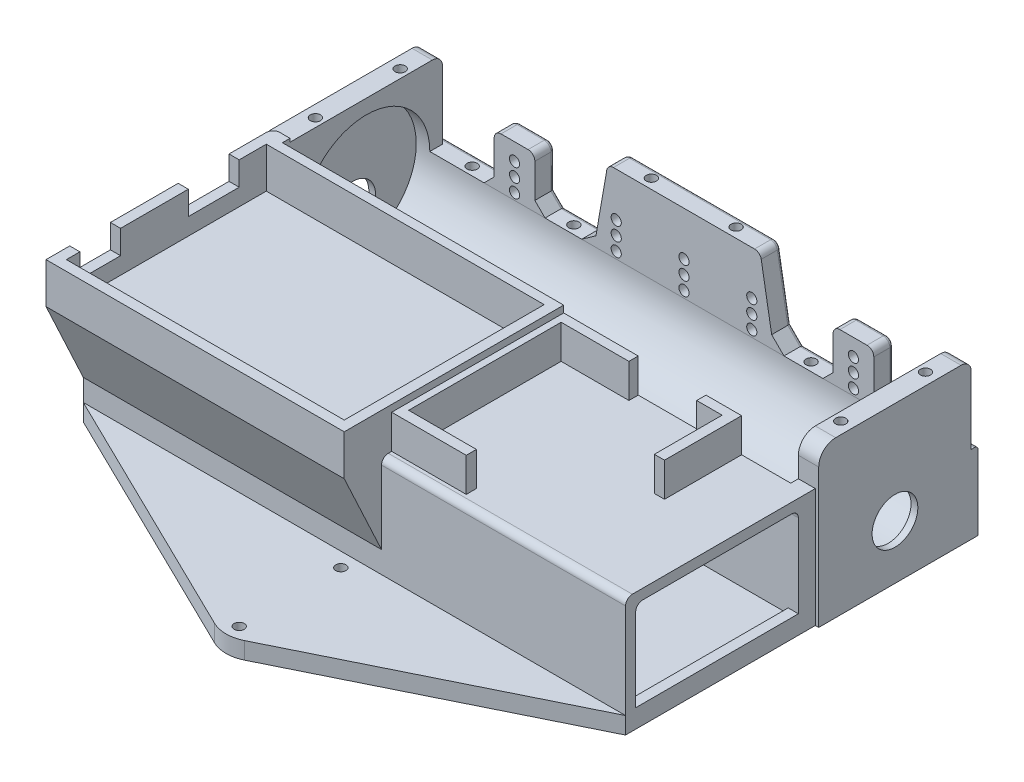
SolidWorks part; units mm, degrees
note: The reader was unsure of these and kept them because the rebuilt part matched: shared geometry of "Sketch4<3>", "Sketch7<3>".
ref_plane "Front Plane" through (0, 0, 0) normal (0, 0, 1) x (1, 0, 0)
ref_plane "Top Plane" through (0, 0, 0) normal (0, 1, 0) x (1, 0, 0)
ref_plane "Right Plane" through (0, 0, 0) normal (1, 0, 0) x (0, 0, -1)
sketch "Size Max" plane through (0, 0, 0) normal (0, 1, 0) x (1, 0, 0)
  line L0 (0, 0) -> (0, -200) construction
  line L1 (0, -200) -> (200, -200) construction
  line L2 (200, 0) -> (200, -200) construction
  line L3 (0, 0) -> (200, 0) construction
  dimension "D1" = 200
  dimension "D2" = 200
sketch "Sketch2" plane through (0, 0, 0) normal (0, 1, 0) x (1, 0, 0)
  line L1 (35.7355, -23.0024) -> (98.2355, -23.0024)
  line L2 (35.7355, -23.0024) -> (35.7355, -58.0024)
  line L3 (35.7355, -58.0024) -> (98.2355, -58.0024)
  line L4 (98.2355, -23.0024) -> (98.2355, -58.0024)
  line L5 (98.2355, -23.0024) -> (160.7355, -23.0024)
  line L6 (98.2355, -23.0024) -> (98.2355, -58.0024)
  line L7 (98.2355, -58.0024) -> (160.7355, -58.0024)
  line L8 (160.7355, -23.0024) -> (160.7355, -58.0024)
  line L10 (10.7355, -29.7764) -> (35.7355, -29.7764)
  line L11 (10.7355, -29.7764) -> (10.7355, -49.7764)
  line L12 (10.7355, -49.7764) -> (35.7355, -49.7764)
  line L13 (35.7355, -29.7764) -> (35.7355, -49.7764)
  line L14 (160.7355, -29.5967) -> (185.7355, -29.5967)
  line L15 (160.7355, -29.5967) -> (160.7355, -49.5967)
  line L16 (160.7355, -49.5967) -> (185.7355, -49.5967)
  line L17 (185.7355, -29.5967) -> (185.7355, -49.5967)
  dimension "D1" = 25
  dimension "D2" = 35
  dimension "D3" = 62.5
  dimension "D4" = 25
  dimension "D5" = 20
  dimension "D6" = 20
sketch "Sketch3" plane through (0, 0, 0) normal (0, 1, 0) x (1, 0, 0)
  line L1 (23.5968, -8.0243) -> (183.5968, -8.0243)
  line L2 (23.5968, -8.0243) -> (23.5968, -158.0243)
  line L3 (23.5968, -158.0243) -> (183.5968, -158.0243)
  line L4 (183.5968, -8.0243) -> (183.5968, -158.0243)
  dimension "D1" = 160
  dimension "D2" = 150
extrude "Boss-Extrude1" add sketch "Sketch3" along normal blind 3
sketch "Sketch4" plane through (183.5968, 0, 0) normal (1, 0, 0) x (0, 0, -1)
  line L0 (-53.0243, 43) -> (-8.0243, 3) construction
  line L1 (-8.0243, 3) -> (-53.0243, 3)
  line L2 (-8.0243, 3) -> (-8.0243, 43)
  line L3 (-8.0243, 43) -> (-53.0243, 43)
  line L4 (-53.0243, 3) -> (-53.0243, 43)
  line L5 (-30.5243, 43) -> (-30.5243, 3) construction
  circle A0 centre (-30.5243, 23) radius 18.75
  circle A1 centre (-30.5243, 16) radius 6.75
  line M10 (-8.0243, 3) -> (-158.0243, 3)
  dimension "D2" = 37.5
  dimension "D3" = 13.5
  dimension "D1" = 40
  dimension "D4" = 7
  dimension "D5" = 45
extrude "Boss-Extrude2" add sketch "Sketch4" against normal blind 1 contours L4 L2 L3 A0 M10 | A0 A1
extrude "Boss-Extrude3" add sketch "Sketch4<3>" against normal blind 5 contours L4 L2 L3 A0 M10
sketch "Sketch4<3>" plane through (183.5968, 0, 0) normal (1, 0, 0) x (0, 0, -1) same geometry as "Sketch4"
sketch "Sketch7" plane through (23.5968, 0, 0) normal (-1, 0, 0) x (0, 0, 1)
  line L1 (8.0243, 3) -> (53.0243, 3)
  line L2 (8.0243, 3) -> (8.0243, 43)
  line L3 (8.0243, 43) -> (53.0243, 43)
  line L4 (53.0243, 3) -> (53.0243, 43)
  circle A0 centre (30.5243, 23) radius 18.75
  circle A1 centre (30.5243, 23) radius 18.75 construction
  circle A2 centre (30.5243, 16) radius 6.75
  circle A3 centre (30.5243, 16) radius 6.75 construction
  line M8 (158.0243, 3) -> (8.0243, 3)
  dimension "D1" = 13.5
extrude "Boss-Extrude4" add sketch "Sketch7" against normal blind 1 contours L4 L3 L2 A0 M8 | A0 A2
extrude "Boss-Extrude5" add sketch "Sketch7<3>" against normal blind 5 contours L4 L3 L2 A0 M8 | A0 A2
sketch "Sketch7<3>" plane through (23.5968, 0, 0) normal (-1, 0, 0) x (0, 0, 1) same geometry as "Sketch7"
sketch "Sketch8" plane through (0, 43, 0) normal (0, 1, 0) x (1, 0, 0)
  line L1 (23.5968, -8.0243) -> (28.5968, -8.0243)
  line L2 (23.5968, -8.0243) -> (23.5968, -53.0243)
  line L3 (23.5968, -53.0243) -> (28.5968, -53.0243)
  line L4 (28.5968, -8.0243) -> (28.5968, -53.0243)
  line L5 (178.5968, -53.0243) -> (183.5968, -53.0243)
  line L6 (178.5968, -53.0243) -> (178.5968, -8.0243)
  line L7 (178.5968, -8.0243) -> (183.5968, -8.0243)
  line L8 (183.5968, -53.0243) -> (183.5968, -8.0243)
extrude "Boss-Extrude6" add sketch "Sketch8" along normal blind 3
sketch "Sketch10" plane through (183.5968, 0, 0) normal (1, 0, 0) x (0, 0, -1)
  line L0 (-53.0243, 3) -> (-53.0243, 46) construction
  line L1 (-109.0243, 35) -> (-53.0243, 35)
  line L2 (-109.0243, 35) -> (-109.0243, 3)
  line L3 (-109.0243, 3) -> (-53.0243, 3)
  line L4 (-53.0243, 35) -> (-53.0243, 3)
  line L5 (-158.0243, 3) -> (-53.0243, 3) construction
  line L7 (-106.0243, 32) -> (-58.0243, 32)
  line L8 (-106.0243, 32) -> (-106.0243, 4)
  line L9 (-106.0243, 4) -> (-58.0243, 4)
  line L10 (-58.0243, 32) -> (-58.0243, 4)
  dimension "D1" = 48
  dimension "D2" = 5
  dimension "D3" = 28
  dimension "D4" = 3
  dimension "D5" = 3
  dimension "D6" = 1
extrude "Boss-Extrude7" add sketch "Sketch10" against normal up to surface (160 mm away) separate body contours L8 L7 L10 L9 | L2 L1 L4 L3 up to face at (23.5968, 16.3333, 73.0243)
sketch "Sketch11" plane through (23.5968, 0, 0) normal (-1, 0, 0) x (0, 0, 1)
  line L0 (58.0243, 32) -> (106.0243, 32) construction
  line L1 (58.0243, 32) -> (106.0243, 32)
  line L2 (58.0243, 32) -> (58.0243, 4)
  line L3 (58.0243, 4) -> (106.0243, 4)
  line L4 (106.0243, 32) -> (106.0243, 4)
  line L5 (58.0243, 4) -> (58.0243, 32) construction
extrude "Boss-Extrude8" add sketch "Sketch11" against normal blind 2
sketch "Sketch12" plane through (0, 4, 0) normal (0, 1, 0) x (1, 0, 0)
  line L0 (183.5968, -106.0243) -> (183.5968, -58.0243) construction
  line L1 (183.5968, -106.0243) -> (180.5968, -106.0243)
  line L2 (183.5968, -106.0243) -> (183.5968, -58.0243)
  line L3 (183.5968, -58.0243) -> (180.5968, -58.0243)
  line L4 (180.5968, -106.0243) -> (180.5968, -58.0243)
  line L5 (25.5968, -58.0243) -> (183.5968, -58.0243) construction
  line L6 (25.5968, -106.0243) -> (183.5968, -106.0243) construction
  dimension "D1" = 3
extrude "Boss-Extrude9" add sketch "Sketch12" along normal blind 1.5
sketch "Sketch13" plane through (0, 35, 0) normal (0, 1, 0) x (1, 0, 0)
  line L0 (28.5968, -53.0243) -> (178.5968, -53.0243) construction
  line L5 (23.5968, -53.0243) -> (23.5968, -109.0243) construction
  line L6 (23.5968, -120.0243) -> (111.5968, -120.0243)
  line L7 (23.5968, -120.0243) -> (23.5968, -53.0243)
  line L8 (23.5968, -53.0243) -> (111.5968, -53.0243)
  line L9 (111.5968, -120.0243) -> (111.5968, -53.0243)
  line L10 (26.5968, -117.0243) -> (108.5968, -117.0243)
  line L11 (26.5968, -117.0243) -> (26.5968, -58.0243)
  line L12 (26.5968, -58.0243) -> (108.5968, -58.0243)
  line L13 (108.5968, -117.0243) -> (108.5968, -58.0243)
  dimension "D3" = 59
  dimension "D4" = 82
  dimension "D5" = 5
  dimension "D6" = 3
  dimension "D7" = 3
  dimension "D8" = 3
extrude "Boss-Extrude10" add sketch "Sketch13" along normal blind 12
sketch "Sketch14" plane through (0, 47, 0) normal (0, 1, 0) x (1, 0, 0)
  line L0 (26.5968, -117.0243) -> (108.5968, -117.0243) construction
  line L1 (23.5968, -66.0243) -> (26.5968, -66.0243)
  line L2 (23.5968, -66.0243) -> (23.5968, -81.0243)
  line L3 (23.5968, -81.0243) -> (26.5968, -81.0243)
  line L4 (26.5968, -66.0243) -> (26.5968, -81.0243)
  line L7 (23.5968, -101.0243) -> (26.5968, -101.0243)
  line L8 (23.5968, -101.0243) -> (23.5968, -113.0243)
  line L9 (23.5968, -113.0243) -> (26.5968, -113.0243)
  line L10 (26.5968, -101.0243) -> (26.5968, -113.0243)
  line L11 (108.5968, -58.0243) -> (26.5968, -58.0243) construction
  line L12 (23.5968, -53.0243) -> (23.5968, -120.0243) construction
  line L13 (26.5968, -58.0243) -> (26.5968, -117.0243) construction
  dimension "D1" = 8
  dimension "D2" = 15
  dimension "D3" = 4
  dimension "D4" = 12
extrude "Cut-Extrude2" cut sketch "Sketch14" against normal offset from surface (7 mm away) 5 up to face at (67.5968, 35, 83.5243)
sketch "Sketch15" plane through (178.5968, 0, 0) normal (-1, 0, 0) x (0, 0, 1)
  line L0 (8.0243, 23) -> (11.7743, 23)
  line L1 (8.0243, 46) -> (8.0243, 0) construction
  line L2 (53.0243, 23) -> (53.0243, 0)
  line L3 (0, 0) -> (200, 0) construction
  line L4 (53.0243, 0) -> (8.0243, 0)
  line L5 (8.0243, 0) -> (8.0243, 23)
  line L6 (53.0243, 3) -> (53.0243, 35) construction
  line L7 (49.2743, 23) -> (53.0243, 23)
  circle A0 centre (30.5243, 23) radius 18.75
  circle A1 centre (30.5243, 23) radius 18.75 construction
  circle M6 centre (30.5243, 23) radius 18.75
  line M7 (53.0243, 3) -> (53.0243, 35)
  line M10 (8.0243, 46) -> (8.0243, 3)
  line M11 (8.0243, 3) -> (53.0243, 3)
sketch "Sketch16" plane through (0, 35, 0) normal (0, 1, 0) x (1, 0, 0)
  line L0 (28.5968, -53.0243) -> (178.5968, -53.0243) construction
  line L1 (113.5968, -58.0243) -> (161.0968, -58.0243)
  line L2 (113.5968, -58.0243) -> (113.5968, -103.0243)
  line L3 (113.5968, -103.0243) -> (161.0968, -103.0243)
  line L4 (161.0968, -58.0243) -> (161.0968, -103.0243)
  line L5 (110.5968, -53.0243) -> (164.0968, -53.0243)
  line L6 (110.5968, -53.0243) -> (110.5968, -106.0243)
  line L7 (110.5968, -106.0243) -> (164.0968, -106.0243)
  line L8 (164.0968, -53.0243) -> (164.0968, -106.0243)
  line L9 (111.5968, -53.0243) -> (23.5968, -53.0243) construction
  dimension "D1" = 45
  dimension "D2" = 47.5
  dimension "D3" = 5
  dimension "D4" = 3
  dimension "D5" = 3
  dimension "D6" = 3
extrude "Boss-Extrude12" add sketch "Sketch16" along normal blind 10
sketch "Sketch17" plane through (0, 45, 0) normal (0, 1, 0) x (1, 0, 0)
  line L0 (113.5968, -103.0243) -> (161.0968, -103.0243) construction
  line L1 (133.5968, -103.0243) -> (153.5968, -103.0243)
  line L2 (133.5968, -103.0243) -> (133.5968, -106.0243)
  line L3 (133.5968, -106.0243) -> (153.5968, -106.0243)
  line L4 (153.5968, -103.0243) -> (153.5968, -106.0243)
  line L5 (111.5968, -106.0243) -> (164.0968, -106.0243) construction
  line L6 (113.5968, -58.0243) -> (113.5968, -103.0243) construction
  line L7 (164.0968, -53.0243) -> (111.5968, -53.0243) construction
  line L8 (133.5968, -53.0243) -> (153.5968, -53.0243)
  line L9 (133.5968, -53.0243) -> (133.5968, -58.0243)
  line L10 (133.5968, -58.0243) -> (153.5968, -58.0243)
  line L11 (153.5968, -53.0243) -> (153.5968, -58.0243)
  line L12 (161.0968, -58.0243) -> (113.5968, -58.0243) construction
  line L13 (161.0968, -103.0243) -> (161.0968, -58.0243) construction
  line L14 (161.0968, -98.0243) -> (164.0968, -98.0243)
  line L15 (161.0968, -98.0243) -> (161.0968, -78.0243)
  line L16 (161.0968, -78.0243) -> (164.0968, -78.0243)
  line L17 (164.0968, -98.0243) -> (164.0968, -78.0243)
  line L18 (164.0968, -106.0243) -> (164.0968, -53.0243) construction
  dimension "D1" = 20
  dimension "D2" = 20
  dimension "D3" = 20
  dimension "D4" = 20
  dimension "D5" = 20
  dimension "D6" = 5
extrude "Cut-Extrude3" cut sketch "Sketch17" against normal up to surface (10 mm away) up to face at (137.3468, 35, 80.5243)
extrude "Boss-Extrude11" add sketch "Sketch15" along normal up to surface (150 mm away) contours L7 L0 M6 M10 M11 M7 up to face at (28.5968, 23, 49.2743)
sketch "Sketch29" plane through (183.5968, 0, 0) normal (1, 0, 0) x (0, 0, -1)
  line L0 (-8.0243, 23) -> (-11.7743, 23) construction
  line L1 (-8.0243, 0) -> (-6.0243, 0)
  line L2 (-8.0243, 0) -> (-8.0243, 23)
  line L3 (-8.0243, 23) -> (-6.0243, 23)
  line L4 (-6.0243, 0) -> (-6.0243, 23)
  dimension "D1" = 2
extrude "Boss-Extrude17" add sketch "Sketch29" against normal up to surface (160 mm away) up to face at (23.5968, 33.8889, 89.9132)
sketch "Sketch36" plane through (183.5968, 0, 0) normal (1, 0, 0) x (0, 0, -1)
  line L0 (-53.0243, 46) -> (-53.0243, 0)
  line L1 (0, 0) -> (-200, 0) construction
  line L2 (-53.0243, 0) -> (-6.0243, 0)
  line L3 (-6.0243, 0) -> (-6.0243, 23)
  line L4 (-6.0243, 23) -> (-8.0243, 23)
  line L5 (-8.0243, 23) -> (-8.0243, 46)
  line L6 (-8.0243, 46) -> (-53.0243, 46)
  line L7 (-8.0243, 46) -> (-8.0243, 23) construction
  circle A0 centre (-30.5243, 16) radius 6.75
  circle A1 centre (-30.5243, 16) radius 6.75 construction
extrude "Boss-Extrude18" add sketch "Sketch36" along normal blind 1
sketch "Sketch39" plane through (23.5968, 0, 0) normal (-1, 0, 0) x (0, 0, 1)
  line L0 (8.0243, 46) -> (8.0243, 23)
  line L1 (8.0243, 46) -> (53.0243, 46) construction
  line L2 (8.0243, 46) -> (8.0243, 23) construction
  line L3 (8.0243, 23) -> (6.0243, 23)
  line L4 (6.0243, 23) -> (6.0243, 0)
  line L5 (6.0243, 0) -> (53.0243, 0)
  line L6 (0, 0) -> (200, 0) construction
  line L7 (53.0243, 0) -> (53.0243, 46)
  line L8 (53.0243, 46) -> (8.0243, 46)
  line L9 (53.0243, 46) -> (53.0243, 0) construction
  circle A0 centre (30.5243, 16) radius 6.75
  circle A1 centre (30.5243, 16) radius 6.75 construction
extrude "Boss-Extrude19" add sketch "Sketch39" along normal blind 1
fillet "Fillet1" radius 3 2 edges at (25.5968, 46, 8.0243) (181.5968, 46, 8.0243)
fillet "Fillet3" radius 2 1 edges at (23.5968, 46.5, 53.0243)
sketch "Sketch18" plane through (0, 23, 0) normal (0, 1, 0) x (1, 0, 0)
  line L0 (28.5968, -11.7743) -> (178.5968, -11.7743) construction
  line L1 (81.0968, -11.7743) -> (126.0968, -11.7743)
  line L2 (81.0968, -11.7743) -> (81.0968, -6.0243)
  line L3 (81.0968, -6.0243) -> (126.0968, -6.0243)
  line L4 (126.0968, -11.7743) -> (126.0968, -6.0243)
  line L6 (22.5968, -6.0243) -> (184.5968, -6.0243) construction
  line L7 (103.5968, -6.0243) -> (103.5968, -11.7743) construction
  point P8 (103.5968, -6.0243)
  dimension "D1" = 45
extrude "Boss-Extrude13" add sketch "Sketch18" along normal up to surface (23 mm away) up to face at (24.9662, 46, 41.2508)
sketch "Sketch20" plane through (0, 46, 0) normal (0, 1, 0) x (1, 0, 0)
  line L0 (81.0968, -8.8993) -> (126.0968, -8.8993) construction
  line L1 (81.0968, -6.0243) -> (81.0968, -11.7743) construction
  line L2 (126.0968, -11.7743) -> (126.0968, -6.0243) construction
  circle A0 centre (91.0968, -8.8993) radius 1.5
  circle A1 centre (116.0968, -8.8993) radius 1.5
  dimension "D1" = 3
  dimension "D2" = 3
  dimension "D4" = 10
  dimension "D3" = 25
extrude "Cut-Extrude5" cut sketch "Sketch20" against normal blind 15
sketch "Sketch21" plane through (0, 3, 0) normal (0, 1, 0) x (1, 0, 0)
  line L0 (183.5968, -109.0243) -> (103.8242, -148.2517)
  line L1 (103.8242, -148.2517) -> (23.5968, -109.0243)
  line L2 (23.5968, -109.0243) -> (23.5968, -158.0243)
  line L3 (23.5968, -158.0243) -> (183.5968, -158.0243)
  line L4 (23.5968, -158.0243) -> (183.5968, -158.0243) construction
  line L5 (183.5968, -158.0243) -> (183.5968, -109.0243) construction
  line L6 (183.5968, -158.0243) -> (183.5968, -109.0243)
  line L7 (103.8242, -158.0243) -> (103.8242, -129.4288) construction
extrude "Cut-Extrude6" cut sketch "Sketch21" against normal through all
sketch "Sketch23" plane through (0, 3, 0) normal (0, 1, 0) x (1, 0, 0)
  line L0 (23.5968, -109.0243) -> (183.5968, -109.0243)
  line L1 (183.5968, -109.0243) -> (103.8242, -148.2517)
  line L2 (183.5968, -109.0243) -> (103.8242, -148.2517) construction
  line L3 (103.8242, -148.2517) -> (23.5968, -109.0243)
  line L4 (103.8242, -148.2517) -> (23.5968, -109.0243) construction
extrude "Boss-Extrude14" add sketch "Sketch23" along normal blind 2
sketch "Sketch22" plane through (0, 5, 0) normal (0, 1, 0) x (1, 0, 0)
  line L1 (103.8242, -148.2517) -> (103.8242, -136.0313) construction
  circle A0 centre (103.8242, -143.2517) radius 1.5
  circle A1 centre (103.8242, -113.2517) radius 1.5
  dimension "D1" = 3
  dimension "D2" = 3
  dimension "D3" = 30
  dimension "D4" = 5
extrude "Cut-Extrude7" cut sketch "Sketch22" against normal through all
fillet "Fillet4" radius 10 1 edges at (103.8242, 2.5, 148.2517)
sketch "Sketch24" plane through (0, 0, 8.0243) normal (0, 0, -1) x (-1, 0, 0)
  line L9 (-126.0968, 46) -> (-130.0968, 23)
  line L10 (-126.0968, 23) -> (-184.5968, 23) construction
  line L11 (-130.0968, 23) -> (-126.0968, 23)
  line L12 (-126.0968, 23) -> (-126.0968, 46)
  line L13 (-81.0968, 46) -> (-81.0968, 23)
  line L14 (-81.0968, 23) -> (-77.0968, 23)
  line L15 (-28.5968, 23) -> (-178.5968, 23) construction
  line L16 (-77.0968, 23) -> (-81.0968, 46)
  dimension "D1" = 4
  dimension "D2" = 4
extrude "Boss-Extrude15" add sketch "Sketch24" against normal up to surface and the other way up to surface up to face at (103.5968, 34.5, 11.7743) other way up to face at (103.5968, 23, 6.0243)
sketch "Sketch25" plane through (0, 35, 0) normal (0, 1, 0) x (1, 0, 0)
  line L1 (144.9183, -89.3587) -> (174.8651, -89.3587)
  line L2 (144.9183, -89.3587) -> (144.9183, -115.0684)
  line L3 (144.9183, -115.0684) -> (174.8651, -115.0684)
  line L4 (174.8651, -89.3587) -> (174.8651, -115.0684)
extrude "Cut-Extrude9" cut sketch "Sketch25" along normal up to surface (10 mm away) up to face at (159.5968, 45, 102.3576)
fillet "Fillet5" radius 5 1 edges at (181.5968, 46, 53.0243)
sketch "Sketch26" plane through (23.5968, 0, 0) normal (-1, 0, 0) x (0, 0, 1)
  line L0 (120.0243, 35) -> (109.0243, 11.4104)
  line L1 (109.0243, 5) -> (109.0243, 35) construction
  line L2 (109.0243, 11.4104) -> (109.0243, 35)
  line L3 (109.0243, 35) -> (120.0243, 35)
  dimension "D1" = 25
extrude "Boss-Extrude16" add sketch "Sketch26" against normal up to surface (88 mm away) up to face at (111.5968, 41.2857, 95.31)
sketch "Sketch28" plane through (0, 46, 0) normal (0, 1, 0) x (1, 0, 0)
  line L0 (181.0968, -18.0243) -> (181.0968, -43.0243) construction
  line L1 (176.0172, -11.7743) -> (176.0172, -49.2743) construction
  line L2 (130.0968, -11.7743) -> (178.5968, -11.7743) construction
  line L3 (28.5968, -49.2743) -> (178.5968, -49.2743) construction
  line L4 (176.0172, -30.5243) -> (199.1331, -30.5243) construction
  line L5 (103.5968, -6.0243) -> (103.5968, -38.9106) construction
  line L6 (81.0968, -6.0243) -> (126.0968, -6.0243) construction
  line L7 (178.5968, -11.7743) -> (178.5968, -49.2743) construction
  line L8 (26.0968, -18.0243) -> (26.0968, -43.0243) construction
  circle A0 centre (181.0968, -18.0243) radius 1.5
  circle A1 centre (181.0968, -43.0243) radius 1.5
  circle A2 centre (26.0968, -43.0243) radius 1.5
  circle A3 centre (26.0968, -18.0243) radius 1.5
  point P12 (181.0968, -30.5243)
  dimension "D1" = 3
  dimension "D2" = 25
  dimension "D3" = 2.5
extrude "Cut-Extrude11" cut sketch "Sketch28" against normal blind 10
fillet "Fillet6" radius 2 2 edges at (104.5968, 32, 106.0243) (104.5968, 32, 58.0243)
sketch "Sketch30" plane through (0, 23, 0) normal (0, 1, 0) x (1, 0, 0)
  line L0 (138.5968, -9.2743) -> (168.5968, -9.2743) construction
  line L1 (183.5968, -6.0243) -> (183.5968, -8.0243) construction
  line L2 (28.5968, -30.5243) -> (178.5968, -30.5243) construction
  line L3 (28.5968, -49.2743) -> (28.5968, -11.7743) construction
  line L4 (178.5968, -11.7743) -> (178.5968, -49.2743) construction
  line L5 (138.5968, -51.7743) -> (168.5968, -51.7743) construction
  line L6 (103.5968, -30.5243) -> (103.5968, -14.8823) construction
  line L7 (68.5968, -51.7743) -> (38.5968, -51.7743) construction
  line L8 (68.5968, -9.2743) -> (38.5968, -9.2743) construction
  line L9 (130.0968, -11.7743) -> (178.5968, -11.7743) construction
  circle A0 centre (138.5968, -9.2743) radius 1.5
  circle A1 centre (168.5968, -9.2743) radius 1.5
  circle A2 centre (168.5968, -51.7743) radius 1.5
  circle A3 centre (138.5968, -51.7743) radius 1.5
  circle A4 centre (68.5968, -51.7743) radius 1.5
  circle A5 centre (38.5968, -51.7743) radius 1.5
  circle A6 centre (38.5968, -9.2743) radius 1.5
  circle A7 centre (68.5968, -9.2743) radius 1.5
  dimension "D1" = 3
  dimension "D2" = 3
  dimension "D3" = 30
  dimension "D4" = 15
  dimension "D5" = 2.5
extrude "Cut-Extrude12" cut sketch "Sketch30" against normal blind 10
sketch "Sketch33" plane through (0, 47, 0) normal (0, 1, 0) x (1, 0, 0)
  line L0 (178.5968, -11.0243) -> (178.5968, -48.0243) construction
  line L1 (28.5968, -49.2743) -> (178.5968, -49.2743)
  line L2 (28.5968, -49.2743) -> (28.5968, -55.2743)
  line L3 (28.5968, -55.2743) -> (178.5968, -55.2743)
  line L4 (178.5968, -49.2743) -> (178.5968, -55.2743)
  dimension "D1" = 6
extrude "Cut-Extrude15" cut sketch "Sketch33" against normal up to surface (24 mm away) up to face at (103.5968, 23, 51.4826)
sketch "Sketch40" plane through (0, 23, 0) normal (0, 1, 0) x (1, 0, 0)
  line L0 (130.0968, -6.0243) -> (184.5968, -6.0243) construction
  line L1 (147.5968, -6.0243) -> (159.5968, -6.0243)
  line L2 (147.5968, -6.0243) -> (147.5968, -11.7743)
  line L3 (147.5968, -11.7743) -> (159.5968, -11.7743)
  line L4 (159.5968, -6.0243) -> (159.5968, -11.7743)
  line L5 (130.0968, -11.7743) -> (178.5968, -11.7743) construction
  line L6 (184.5968, -6.0243) -> (184.5968, -8.0243) construction
  line L7 (22.5968, -6.0243) -> (77.0968, -6.0243) construction
  line L8 (47.5968, -6.0243) -> (59.5968, -6.0243)
  line L9 (47.5968, -6.0243) -> (47.5968, -11.7743)
  line L10 (47.5968, -11.7743) -> (59.5968, -11.7743)
  line L11 (59.5968, -6.0243) -> (59.5968, -11.7743)
  dimension "D1" = 12
  dimension "D2" = 25
  dimension "D3" = 12
  dimension "D4" = 25
extrude "Boss-Extrude20" add sketch "Sketch40" along normal blind 15
sketch "Sketch34" plane through (0, 0, 6.0243) normal (0, 0, -1) x (-1, 0, 0)
  line L0 (-103.5968, 46) -> (-103.5968, 29.8137) construction
  line L1 (-126.0968, 46) -> (-81.0968, 46) construction
  line L3 (-159.5968, 38) -> (-147.5968, 38) construction
  circle A0 centre (-153.5968, 33) radius 1.5
  circle A1 centre (-153.5968, 29) radius 1.5
  circle A2 centre (-153.5968, 25) radius 1.5
  circle A3 centre (-123.5968, 33) radius 1.5
  circle A4 centre (-123.5968, 29) radius 1.5
  circle A5 centre (-123.5968, 25) radius 1.5
  circle A6 centre (-103.5968, 33) radius 1.5
  circle A7 centre (-103.5968, 29) radius 1.5
  circle A8 centre (-103.5968, 25) radius 1.5
  circle A9 centre (-83.5968, 33) radius 1.5
  circle A10 centre (-83.5968, 29) radius 1.5
  circle A11 centre (-83.5968, 25) radius 1.5
  circle A12 centre (-53.5968, 33) radius 1.5
  circle A13 centre (-53.5968, 29) radius 1.5
  circle A14 centre (-53.5968, 25) radius 1.5
  point P36 (0, 0)
  point P37 (0, 0)
  dimension "D1" = 3
  dimension "D7" = 3
  dimension "D8" = 3
  dimension "D9" = 3
  dimension "D4" = 5
  dimension "D5" = 20
  dimension "D6" = 4
  dimension "D3" = 20
  dimension "D2" = 3
extrude "Cut-Extrude16" cut sketch "Sketch34" against normal blind 8
chamfer "Chamfer1" distance 3 angle 45 2 edges at (130.0968, 23, 8.8993) (77.0968, 23, 8.8993)
chamfer "Chamfer2" distance 3 angle 45 4 edges at (47.5968, 23, 8.8993) (59.5968, 23, 8.8993) (159.5968, 23, 8.8993) (147.5968, 23, 8.8993)
fillet "Fillet8" radius 1 19 edges at (79.3538, 35.9778, 6.0243) (103.5968, 46, 6.0243) (127.781, 36.3158, 6.0243) (33.5968, 23, 6.0243) (173.5968, 23, 6.0243) (159.5968, 32, 6.0243) (161.0968, 24.5, 6.0243) (153.5968, 38, 6.0243) (147.5968, 32, 6.0243) (146.0968, 24.5, 6.0243) (138.8468, 23, 6.0243) (131.281, 24.8158, 6.0243) (47.5968, 32, 6.0243) (53.5968, 38, 6.0243) (59.5968, 32, 6.0243) (61.0968, 24.5, 6.0243) (46.0968, 24.5, 6.0243) (68.0037, 23, 6.0243) (75.5108, 24.4778, 6.0243)
fillet "Fillet9" radius 2 1 edges at (147.5968, 35, 109.0243)
fillet "Fillet10" radius 2 12 edges at (59.5968, 38, 9.3993) (47.5968, 38, 9.3993) (147.5968, 38, 9.3993) (159.5968, 38, 9.3993) (159.3039, 37.7071, 6.3172) (147.8897, 37.7071, 6.3172) (47.8897, 37.7071, 6.3172) (59.3039, 37.7071, 6.3172) (81.3431, 45.7071, 6.3172) (125.8504, 45.7071, 6.3172) (126.0968, 46, 9.3993) (81.0968, 46, 9.3993)
